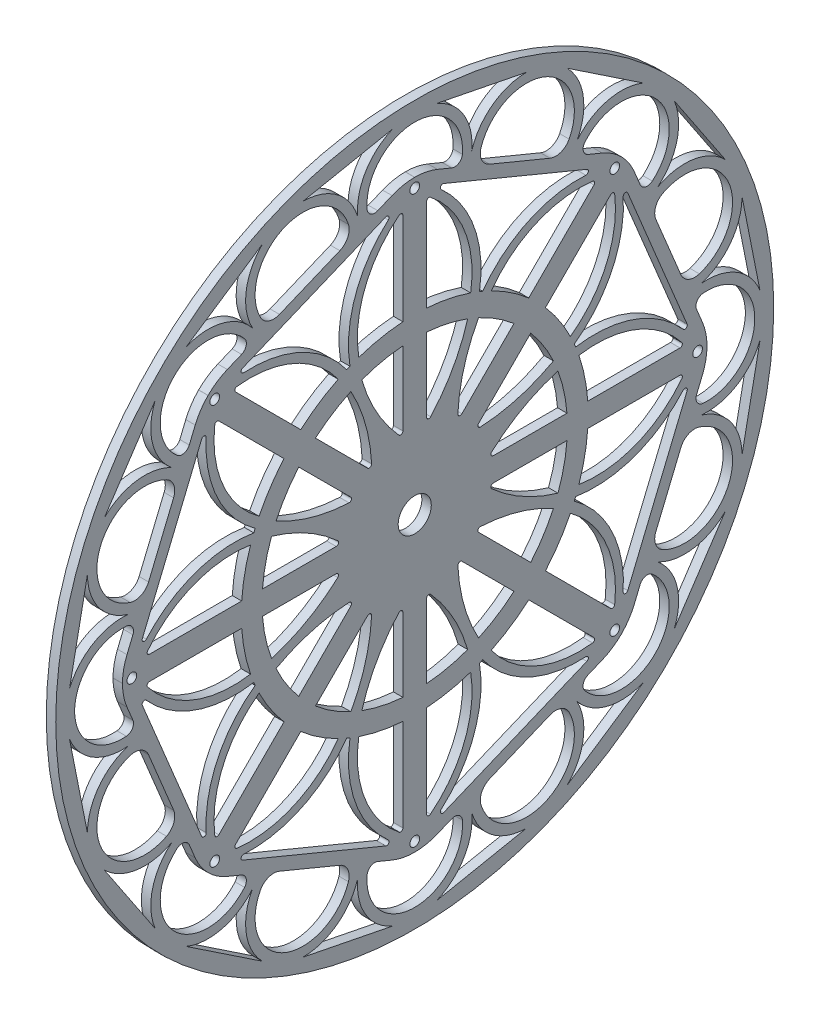
SolidWorks part; units mm, degrees
ref_plane "Front Plane" through (0, 0, 0) normal (1, 0, 0) x (0, 1, 0)
ref_plane "Top Plane" through (0, 0, 0) normal (0, 0, 1) x (0, 1, 0)
ref_plane "Right Plane" through (0, 0, 0) normal (0, 1, 0) x (-1, 0, 0)
sketch "Sketch1" plane through (0, 0, 0) normal (1, 0, 0) x (0, 1, 0)
  line L0 (0, 117.5907) -> (0, 0) construction
  line L1 (83.1492, 83.1492) -> (0, 117.5907) construction
  line L2 (0, 117.5907) -> (-83.1492, 83.1492) construction
  line L4 (-117.5907, 0) -> (-83.1492, -83.1492) construction
  line L5 (-83.1492, -83.1492) -> (0, -117.5907) construction
  line L6 (0, -117.5907) -> (83.1492, -83.1492) construction
  line L7 (83.1492, -83.1492) -> (117.5907, 0) construction
  line L8 (117.5907, 0) -> (83.1492, 83.1492) construction
  line L9 (-83.1492, 83.1492) -> (0, 0) construction
  line L10 (0, 0) -> (-117.5907, 0) construction
  line L11 (-117.5907, 0) -> (-117.6201, 0) construction
  line L12 (-123.5907, 0) -> (-123.5907, 5) construction
  line L14 (-36.2329, 29.1619) -> (-51.4539, 44.3828) construction
  line L15 (-90.9273, 83.8563) -> (-87.3918, 87.3918) construction
  line L16 (-87.3918, 87.3918) -> (-85.9776, 85.9776) construction
  line L18 (-121.6201, 0) -> (-123.5907, 0) construction
  line L19 (-123.5907, 5) -> (-90.9273, 83.8563) construction
  line L20 (-87.1005, 80.0294) -> (-118.1787, 5) construction
  line L21 (-55.2807, 48.2096) -> (-62.699, 30.3003) construction
  line L22 (-59.6103, 24.6914) -> (-36.2329, 29.1619) construction
  line L23 (-67.7667, 5) -> (-51.4539, 44.3828) construction
  line L24 (-59.6103, 24.6914) -> (-46.2411, 5) construction
  line L25 (0, 0) -> (-83.1492, 83.1492)
  line L26 (-55.2807, 48.2096) -> (-84.2721, 77.201) construction
  line L27 (-67.7667, 5) -> (-46.2411, 5) construction
  line L28 (-114.1787, 5) -> (-73.1787, 5) construction
  line L29 (-65.7604, 22.9093) -> (-73.1787, 5) construction
  line L30 (-85.9776, 85.9776) -> (-87.3918, 87.3918)
  line L31 (-83.1492, 83.1492) -> (-88.2348, 70.8713) construction
  line L32 (-87.3918, 87.3918) -> (-90.9273, 83.8563)
  line L33 (-90.9273, 83.8563) -> (-123.5907, 5)
  line L34 (-123.5907, 5) -> (-123.5907, 0)
  line L35 (-123.5907, 0) -> (-121.6201, 0)
  line L36 (-117.6201, 0) -> (0, 0)
  arc A0 (-108.6396, 0) -> (-76.8198, 76.8198) centre (0, 0) ccw construction
  arc A5 (-87.1005, 80.0294) -> (-64.2297, 26.6048) centre (-38.2585, 69.3307) ccw construction
  arc A6 (-114.1787, 5) -> (-65.7604, 22.9093) centre (-76.7606, -21.7561) cw construction
  arc A7 (-84.2721, 77.201) -> (-62.699, 30.3003) centre (-38.8941, 69.6618) ccw construction
  arc A8 (-118.1787, 5) -> (-64.2297, 26.6048) centre (-76.0771, -21.9713) cw construction
  arc A9 (-117.5907, 0) -> (-83.1492, 83.1492) centre (0, 0) ccw construction
  arc A12 (-85.9776, 85.9776) -> (-83.1492, 83.1492) centre (-84.5634, 84.5634) ccw
  arc A13 (-121.6201, 0) -> (-117.6201, 0) centre (-119.6201, 0) cw
  dimension "D1" = 6
  dimension "D8" = 50
  dimension "D9" = 4
  dimension "D12" = 46
  dimension "D13" = 4
  dimension "D4" = 2
  dimension "D11" = 2
  dimension "D2" = 90
  dimension "D3" = 5
  dimension "D5" = 5
  dimension "D7" = 5
  dimension "D10" = 45
extrude "Boss-Extrude3" add sketch "Sketch1" along normal blind 4
sketch "Sketch2" plane through (4, 0, 0) normal (1, 0, 0) x (0, 1, 0)
  line L0 (-84.2721, 77.201) -> (-55.2807, 48.2096)
  line L1 (-55.2807, 48.2096) -> (-62.699, 30.3003)
  line L2 (-65.7604, 22.9093) -> (-73.1787, 5)
  line L3 (-73.1787, 5) -> (-114.1787, 5)
  line L4 (-118.1787, 5) -> (-87.1005, 80.0294)
  arc A0 (-87.1005, 80.0294) -> (-64.2297, 26.6048) centre (-38.2585, 69.3307) ccw
  arc A1 (-62.699, 30.3003) -> (-84.2721, 77.201) centre (-38.8941, 69.6618) cw
  arc A2 (-64.2297, 26.6048) -> (-118.1787, 5) centre (-76.0771, -21.9713) ccw
  arc A3 (-65.7604, 22.9093) -> (-114.1787, 5) centre (-76.7606, -21.7561) ccw
extrude "Cut-Extrude5" cut sketch "Sketch2" against normal blind 4 contours A2 A0 L4 | A1 L1 L0 | L2 A3 L3 region at (4, -71.2812, 52.1242) region at (4, -87.2608, 13.5461) region at (4, -92.9106, 38.4849)
sketch "Sketch4" plane through (4, 0, 0) normal (1, 0, 0) x (0, 1, 0)
  line L0 (0, 0) -> (-83.1492, 83.1492) construction
  line L1 (-67.7667, 5) -> (-51.4539, 44.3828) construction
  line L2 (-117.6201, 0) -> (0, 0) construction
  line L3 (-58.6536, 27.0011) -> (-60.567, 22.3817) construction
  line L5 (-51.4539, 44.3828) -> (-25.2262, 18.1552)
  line L6 (-67.7667, 5) -> (-30.6753, 5)
  line L7 (-51.4539, 44.3828) -> (-58.6536, 27.0011)
  line L8 (-67.7667, 5) -> (-60.567, 22.3817)
  line L9 (-64.2297, 26.6048) -> (-59.6103, 24.6914) construction
  arc A0 (-18.3848, 18.3848) -> (-58.6536, 27.0011) centre (-24.2, 89.6145) cw construction
  arc A1 (-26, 0) -> (-60.567, 22.3817) centre (-80.479, -46.255) ccw construction
  arc A2 (-25.2262, 18.1552) -> (-58.6536, 27.0011) centre (-24.2, 89.6145) cw
  arc A3 (-60.567, 22.3817) -> (-30.6753, 5) centre (-80.479, -46.255) cw
  dimension "D1" = 26
  dimension "D2" = 26
  dimension "D3" = 5
  dimension "D4" = 5
extrude "Cut-Extrude6" cut sketch "Sketch4" against normal up to vertex (4 mm away) contours A2 L7 L5 | A3 L6 L8 up to point (0, -46.2411, 5)
fillet "Fillet3" radius 1 6 edges at (2, -118.1787, 5) (2, -87.1005, 80.0294) (2, -30.6753, 5) (2, -25.2262, 18.1552) (2, -114.1787, 5) (2, -84.2721, 77.201)
fillet "Fillet4" radius 25 2 edges at (2, -90.9273, 83.8563) (2, -123.5907, 5)
pattern_circular "CirPattern2" count 8 over 360 about axis through (4, 0, 0) along (-1, 0, 0) of "Boss-Extrude3", "Cut-Extrude5", "Cut-Extrude6", "Fillet3", "Fillet4"
sketch "Sketch5" plane through (4, 0, 0) normal (1, 0, 0) x (0, 0, -1)
  line L0 (0.0272, -123.5907) -> (0, -146.4823)
  line L1 (0, -146.4823) -> (0, -151.7532)
  line L2 (-87.411, -87.3726) -> (-103.6014, -103.5559)
  line L3 (-103.6014, -103.5559) -> (-107.3293, -107.2821)
  line L4 (-83.8563, -90.9273) -> (-5, -123.5907) construction
  line L5 (-62.7141, -99.6847) -> (-44.4281, -107.259) construction
  line L6 (-44.4281, -107.259) -> (-26.1422, -114.8333) construction
  line L7 (-87.411, -87.3726) -> (-62.7141, -99.6847) construction
  line L8 (-26.1422, -114.8333) -> (0.0272, -123.5907) construction
  line L9 (-103.6014, -103.5559) -> (-87.5988, -117.4032) construction
  line L10 (-21.1068, -144.9537) -> (0, -146.4823) construction
  circle A0 centre (0, 0) radius 151.7532 construction
  arc A1 (-107.3293, -107.2821) -> (0, -151.7532) centre (0, 0) ccw
  circle A2 centre (0, 0) radius 146.4823 construction
  arc A3 (-103.6014, -103.5559) -> (0, -146.4823) centre (0, 0) ccw
  arc A4 (-62.7141, -99.6847) -> (-103.6014, -103.5559) centre (-86.3933, -67.4466) cw
  arc A5 (-44.4281, -107.259) -> (-87.5988, -117.4032) centre (-73.2198, -81.6633) cw
  arc A6 (-26.1422, -114.8333) -> (0, -146.4823) centre (13.3992, -108.7933) ccw
  arc A7 (-44.4281, -107.259) -> (-21.1068, -144.9537) centre (-5.971, -109.5276) ccw
  dimension "D1" = 40
sketch "Sketch7" plane through (4, 0, 0) normal (1, 0, 0) x (0, 1, 0)
  line L0 (-90.9273, 83.8563) -> (-123.5907, 5) construction
  line L1 (-147.8187, 0) -> (-143.8187, 0)
  line L2 (-109.7756, 96.6635) -> (-131.3147, 64.4279)
  line L3 (-138.4109, 47.2961) -> (-145.9744, 9.2717)
  line L4 (-147.8187, 0) -> (-151.8187, 0)
  line L5 (-104.5236, 104.5236) -> (-107.352, 107.352)
  line L6 (-104.5236, 104.5236) -> (-101.6952, 101.6952)
  line L7 (-95.3376, 73.2089) -> (-101.9695, 57.198)
  line L8 (-119.1804, 15.6474) -> (-112.5485, 31.6582)
  circle A0 centre (0, 0) radius 123.5907 construction
  circle A1 centre (0, 0) radius 151.8187 construction
  arc A2 (-147.8187, 0) -> (-104.5236, 104.5236) centre (0, 0) ccw construction
  arc A3 (-68.6633, 102.7619) -> (-104.5236, 104.5236) centre (-87.3918, 87.3918) ccw construction
  arc A4 (-102.7619, 68.6633) -> (-131.3147, 64.4279) centre (-114.1829, 47.2961) ccw construction
  arc A5 (-121.2159, 24.1113) -> (-145.9744, 9.2717) centre (-123.5907, 0) ccw construction
  arc A6 (-102.7619, 68.6633) -> (-109.7756, 96.6635) centre (-87.3918, 87.3918) cw
  arc A7 (-102.7619, 68.6633) -> (-131.3147, 64.4279) centre (-114.1829, 47.2961) ccw
  arc A8 (-121.2159, 24.1113) -> (-145.9744, 9.2717) centre (-123.5907, 0) ccw
  arc A9 (-121.9353, 20.1602) -> (-143.8187, 0) centre (-123.5907, 0) ccw
  arc A10 (-100.4767, 71.9659) -> (-101.6952, 101.6952) centre (-87.3918, 87.3918) cw
  arc A11 (-104.9386, 65.2882) -> (-120.3685, 28.0371) centre (-114.1829, 47.2961) ccw
  arc A12 (-100.4767, 71.9659) -> (-95.3376, 73.2089) centre (-98.3603, 74.4609) ccw
  arc A13 (-104.9386, 65.2882) -> (-101.9695, 57.198) centre (-107.8449, 59.6317) cw
  arc A14 (-120.3685, 28.0371) -> (-112.5485, 31.6582) centre (-118.4238, 34.0919) ccw
  arc A15 (-121.9353, 20.1602) -> (-119.1804, 15.6474) centre (-122.2031, 16.8994) cw
  arc A16 (-107.352, 107.352) -> (-151.8187, 0) centre (0, 0) ccw
  arc A17 (-147.8187, 0) -> (-121.2159, -24.1113) centre (-123.5907, 0) ccw construction
  arc A18 (-138.4109, 47.2961) -> (-121.2159, 24.1113) centre (-114.1829, 47.2961) ccw construction
  arc A19 (-138.4109, 47.2961) -> (-121.2159, 24.1113) centre (-114.1829, 47.2961) ccw
  arc A20 (-109.7756, 96.6635) -> (-102.7619, 68.6633) centre (-87.3918, 87.3918) ccw construction
  dimension "D1" = 4
  dimension "D2" = 4
  dimension "D3" = 4
  dimension "D4" = 4
extrude "Boss-Extrude5" add sketch "Sketch7" against normal blind 4
sketch "Sketch8" plane through (4, 0, 0) normal (1, 0, 0) x (0, 0, -1)
  circle A0 centre (-84.5842, -84.5842) radius 2.05
  dimension "D1" = 4.1
extrude "Cut-Extrude7" cut sketch "Sketch8" against normal through all both and the other way through all
ref_axis "Axis3" through (-0.2, 0, 0) along (1, 0, 0)
pattern_circular "CirPattern4" count 8 over 360 about axis through (-0.2, 0, 0) along (1, 0, 0) of "Cut-Extrude7", "Boss-Extrude5"
sketch "Sketch9" plane through (0, 0, 0) normal (-1, 0, 0) x (0, 0, 1)
  circle A0 centre (0, 0) radius 64.5701
  circle A1 centre (0, 0) radius 73.3493
extrude "Boss-Extrude6" add sketch "Sketch9" against normal up to surface (4 mm away) up to face at (4, -119.6201, -2.05)
sketch "Sketch10" plane through (0, 0, 0) normal (-1, 0, 0) x (0, 0, 1)
  circle A0 centre (0, 0) radius 7
  dimension "D1" = 14
extrude "Cut-Extrude8" cut sketch "Sketch10" against normal blind 10
